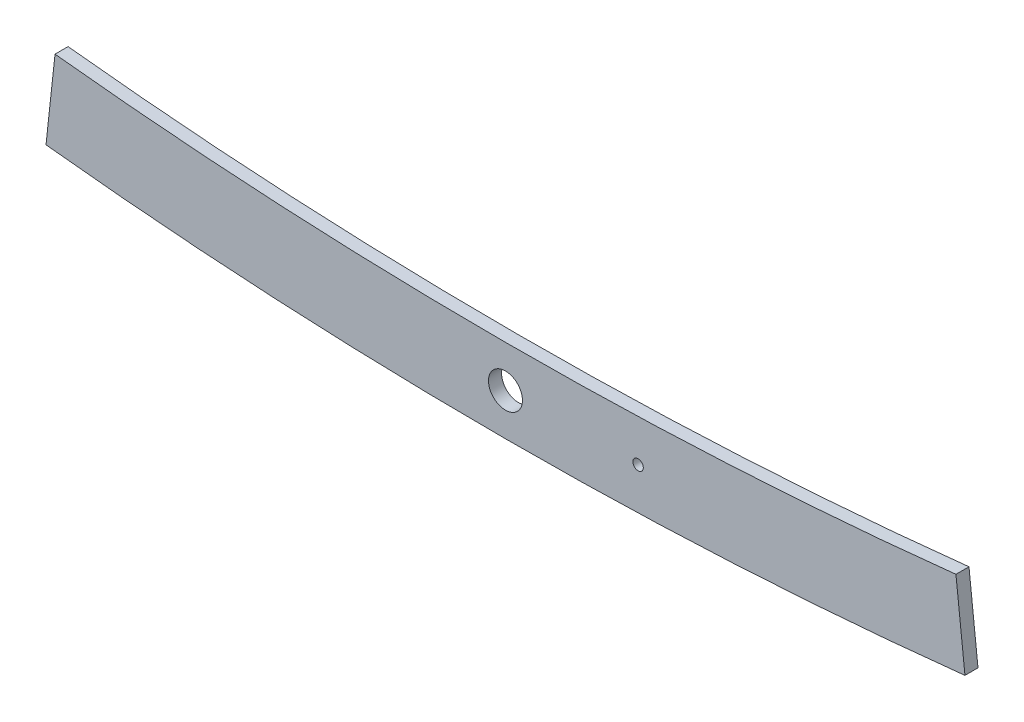
SolidWorks part; units mm, degrees
material "Plain Carbon Steel"
ref_plane "Front Plane" through (0, 0, 0) normal (0, 0, 1) x (1, 0, 0)
ref_plane "Top Plane" through (0, 0, 0) normal (0, 1, 0) x (1, 0, 0)
ref_plane "Right Plane" through (0, 0, 0) normal (1, 0, 0) x (0, 0, -1)
sketch "Sketch1" plane through (0, 0, 0) normal (0, 0, 1) x (1, 0, 0)
  line L0 (88, 4.759) -> (86.2745, 20.6657)
  line L1 (-88, 4.759) -> (-86.2745, 20.6657)
  arc A0 (-88, 4.759) -> (88, 4.759) centre (0, 816) ccw
  arc A1 (-86.2745, 20.6657) -> (86.2745, 20.6657) centre (0, 816) ccw
extrude "Boss-Extrude1" add sketch "Sketch1" along normal mid plane 2.5
sketch "Sketch2" plane through (0, 0, 0) normal (0, 0, 1) x (1, 0, 0)
  circle A0 centre (0, 8) radius 3.25
  dimension "D1" = 6.5
extrude "Cut-Extrude1" cut sketch "Sketch2" against normal mid plane 20
sketch "Sketch3" plane through (0, 0, 0) normal (0, 0, 1) x (1, 0, 0)
  circle A0 centre (25.4, 8.3994) radius 1
  dimension "D1" = 2
extrude "Cut-Extrude2" cut sketch "Sketch3" against normal mid plane 20
